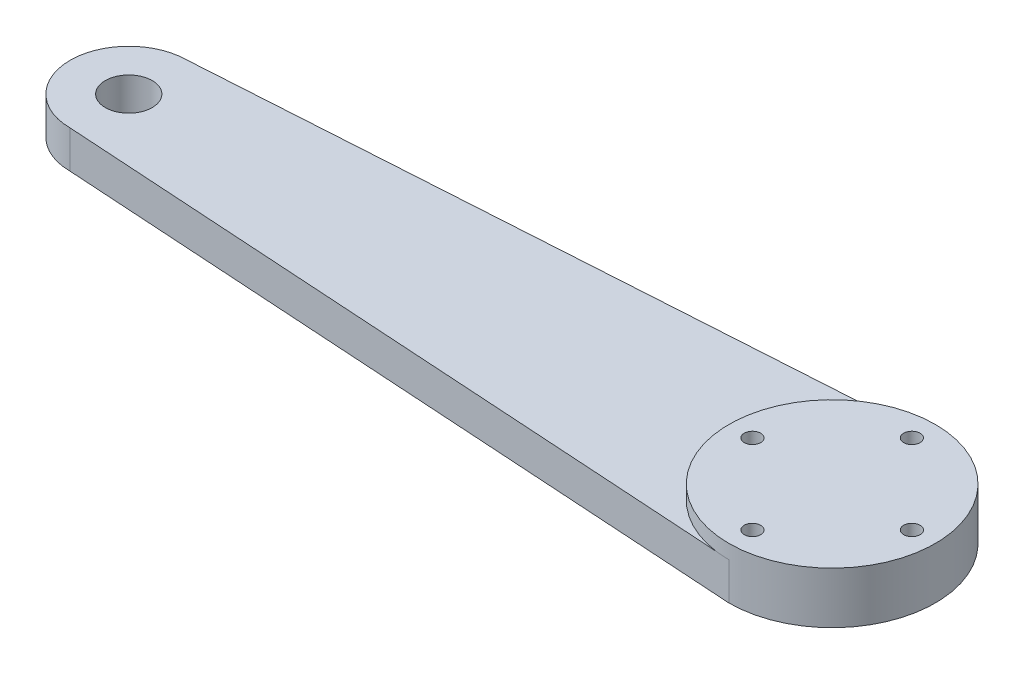
SolidWorks part; units mm, degrees
ref_plane "Front Plane" through (0, 0, 0) normal (0, 0, 1) x (1, 0, 0)
ref_plane "Top Plane" through (0, 0, 0) normal (0, 1, 0) x (1, 0, 0)
ref_plane "Right Plane" through (0, 0, 0) normal (1, 0, 0) x (0, 0, -1)
sketch "Sketch1" plane through (0, 0, 0) normal (0, 1, 0) x (1, 0, 0)
  line L0 (-150, 12.5) -> (0, 22)
  line L1 (-150, -12.5) -> (0, -22)
  arc A0 (0, -22) -> (0, 22) centre (0, 0) ccw
  arc A1 (-150, 12.5) -> (-150, -12.5) centre (-150, 0) ccw
  circle A2 centre (0, 17) radius 1.75
  circle A3 centre (17, 0) radius 1.75
  circle A4 centre (0, -17) radius 1.75
  circle A5 centre (-17, 0) radius 1.75
  circle A6 centre (-150, 0) radius 5
  point P18 (0, 0)
  dimension "D1" = 44
  dimension "D3" = 25
  dimension "D5" = 3.5
  dimension "D7" = 10
  dimension "D2" = 150
  dimension "D4" = 17
  dimension "D6" = 4
extrude "Boss-Extrude1" add sketch "Sketch1" along normal blind 8
sketch "Sketch2" plane through (0, 8, 0) normal (0, 1, 0) x (1, 0, 0)
  circle A0 centre (0, 0) radius 22
  circle A1 centre (-17, 0) radius 1.75 construction
  circle A2 centre (0, -17) radius 1.75 construction
  circle A3 centre (17, 0) radius 1.75 construction
  circle A4 centre (0, 17) radius 1.75 construction
  circle A5 centre (-17, 0) radius 1.75
  circle A6 centre (0, -17) radius 1.75
  circle A7 centre (17, 0) radius 1.75
  circle A8 centre (0, 17) radius 1.75
  dimension "D1" = 44
extrude "Boss-Extrude2" add sketch "Sketch2" along normal blind 3
sketch "Sketch3" plane through (0, 0, 0) normal (0, -1, 0) x (-1, 0, 0)
  circle A0 centre (0, 17) radius 1.75 construction
  circle A1 centre (-17, 0) radius 1.75 construction
  circle A2 centre (0, -17) radius 1.75 construction
  circle A3 centre (17, 0) radius 1.75 construction
  circle A4 centre (0, 17) radius 1.75
  circle A5 centre (-17, 0) radius 1.75
  circle A6 centre (0, -17) radius 1.75
  circle A7 centre (17, 0) radius 1.75
  circle A8 centre (0, 17) radius 3.25
  circle A9 centre (-17, 0) radius 3.25
  circle A10 centre (0, -17) radius 3.25
  circle A11 centre (17, 0) radius 3.25
  dimension "D1" = 1.5
extrude "Cut-Extrude1" cut sketch "Sketch3" against normal blind 4
